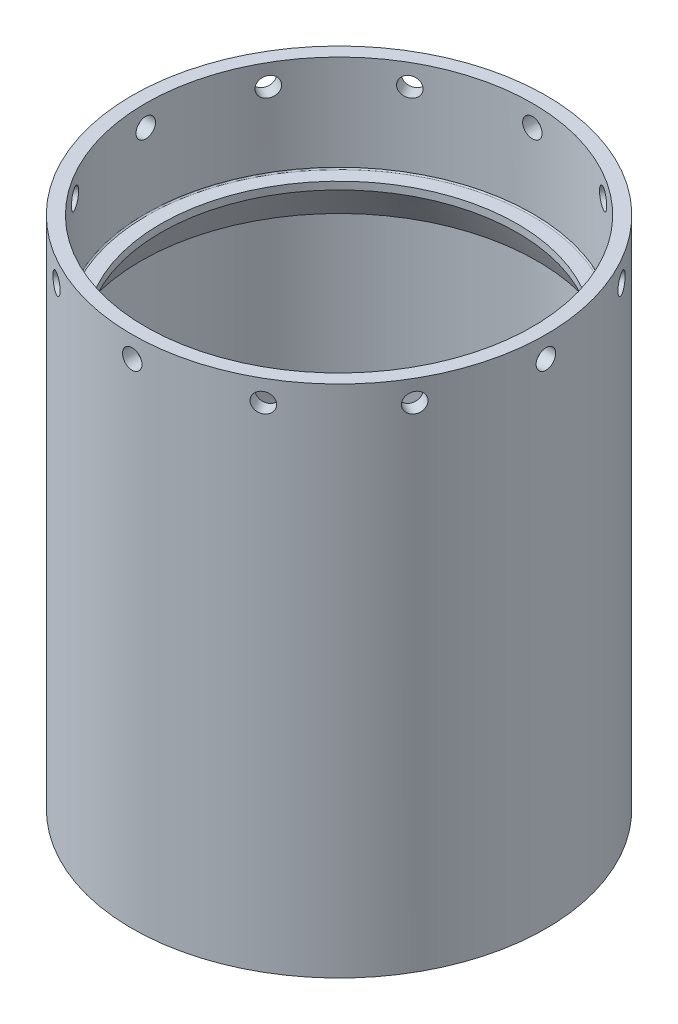
SolidWorks part; units mm, degrees
material "AISI 304"
ref_plane "Front Plane" through (0, 0, 0) normal (0, 0, 1) x (1, 0, 0)
ref_plane "Top Plane" through (0, 0, 0) normal (0, 1, 0) x (1, 0, 0)
ref_plane "Right Plane" through (0, 0, 0) normal (1, 0, 0) x (0, 0, -1)
sketch "Sketch2" plane through (0, 0, 0) normal (0, 0, 1) x (1, 0, 0)
  line L4 (0, 0) -> (0, -101.6) construction
  line L6 (59.69, 0) -> (64.8208, 0)
  line L7 (59.69, 0) -> (59.69, -2.54)
  line L8 (57.15, -139.9369) -> (69.342, -139.9369)
  line L9 (69.342, 32.385) -> (69.342, -139.9369)
  line L12 (64.8208, 0) -> (64.8208, 32.385)
  line L13 (64.8208, 32.385) -> (69.342, 32.385)
  line L14 (59.69, -2.54) -> (66.3575, -14.0884)
  line L15 (66.3575, -14.0884) -> (66.3575, -115.6884)
  line L17 (59.69, -135.5375) -> (59.69, -127.2369)
  line L18 (59.69, -127.2369) -> (66.3575, -115.6884)
  line L19 (59.69, -135.5375) -> (57.15, -139.9369)
  dimension "D5" = 32.385
  dimension "D7" = 129.6416
  dimension "D2" = 119.38
  dimension "D3" = 4.5212
  dimension "D4" = 132.715
  dimension "D8" = 138.684
  dimension "D9" = 30
  dimension "D10" = 2.54
  dimension "D11" = 30
  dimension "D14" = 119.38
  dimension "D15" = 114.3
  dimension "D16" = 30
  dimension "D12" = 12.7
  dimension "D6" = 101.6
  dimension "D13" = 172.3219
revolve "Revolve1" add sketch "Sketch2" angle 360 about L4
fillet "Fillet1" radius 0.4064 1 edges at (-64.8208, 0, 0)
ref_plane "Plane1" through (0, 0, 69.342) normal (0, 0, 1) x (1, 0, 0)
sketch "Sketch3" plane through (0, 0, 69.342) normal (0, 0, 1) x (1, 0, 0)
  line L1 (64.4144, 0) -> (-64.4144, 0) construction
  point P0 (0, 25.3111)
  dimension "D1" = 25.3111
hole_wizard "F (0.257) Injector Hole" positions "Sketch3" profile "Sketch4" hole size "F" standard "ANSI Inch" end condition up to next
sketch "Sketch4" plane through (0, 25.3111, 69.342) normal (1, 0, 0) x (0, -1, 0)
  line L0 (0, 0) -> (0, 4.5212)
  line L1 (0, 4.5212) -> (3.2639, 4.5212)
  line L2 (3.2639, 4.5212) -> (3.2639, 0)
  line L5 (3.2639, 0) -> (0, 0)
  line L11 (0, -6.35) -> (0, 107.95) construction
  dimension "Thru Hole Dia." = 6.5278
  dimension "Thru Hole Depth" = 4.5212
sketch "Sketch5" plane through (0, -139.9369, 0) normal (0, -1, 0) x (1, 0, 0)
  line L0 (0, 64.516) -> (-61.3584, 19.9365) construction
  line L1 (-61.3584, 19.9365) -> (-37.9216, -52.1945) construction
  line L2 (-37.9216, -52.1945) -> (37.9216, -52.1945) construction
  line L3 (37.9216, -52.1945) -> (61.3584, 19.9365) construction
  line L4 (61.3584, 19.9365) -> (0, 64.516) construction
  circle A1 centre (0, 0) radius 64.516 construction
  point P0 (0, 64.516)
  point P8 (61.3584, 19.9365)
  point P10 (37.9216, -52.1945)
  point P12 (-37.9216, -52.1945)
  point P14 (-61.3584, 19.9365)
  dimension "D1" = 129.032
hole_wizard "1/4-20 Tapped Nozzle Hole" positions "Sketch5" profile "Sketch6" tap size "1/4-20" standard "ANSI Inch"
sketch "Sketch6" plane through (0, -139.9369, 64.516) normal (1, 0, 0) x (0, 0, -1)
  line L0 (0, 0) -> (0, 14.2338)
  line L1 (0, 14.2338) -> (2.5527, 12.7)
  line L2 (2.5527, 12.7) -> (2.5527, 6.985)
  line L3 (2.5527, 6.985) -> (3.175, 6.985)
  line L4 (3.175, 6.985) -> (3.175, 0)
  line L5 (3.175, 0) -> (0, 0)
  line L10 (0, 14.2338) -> (-2.5527, 12.7) construction
  line L11 (0, -6.35) -> (0, 107.95) construction
  dimension "Tap Drill Dia." = 5.1054
  dimension "Tap Drill Depth" = 12.7
  dimension "Thread Major Dia." = 6.35
  dimension "Thread Depth" = 6.985
  dimension "Drill Angle" = 118
pattern_circular "CirPattern1" count 12 over 360 about axis through (0, 0, 0) along (0, 1, 0) of "F (0.257) Injector Hole" reverse direction yes
equation "\"length\"= 4in"
equation "\"bearingThickness\"= 0.178in"
equation "\"chamberID\"=5.225"
equation "\"D3@Sketch2\"=\"bearingThickness\""
equation "\"D4@Sketch2\"=\"chamberID\""
equation "\"D6@Sketch2\"=\"length\""
equation "\"D1@Sketch3\"=0.990in+0.0065"
